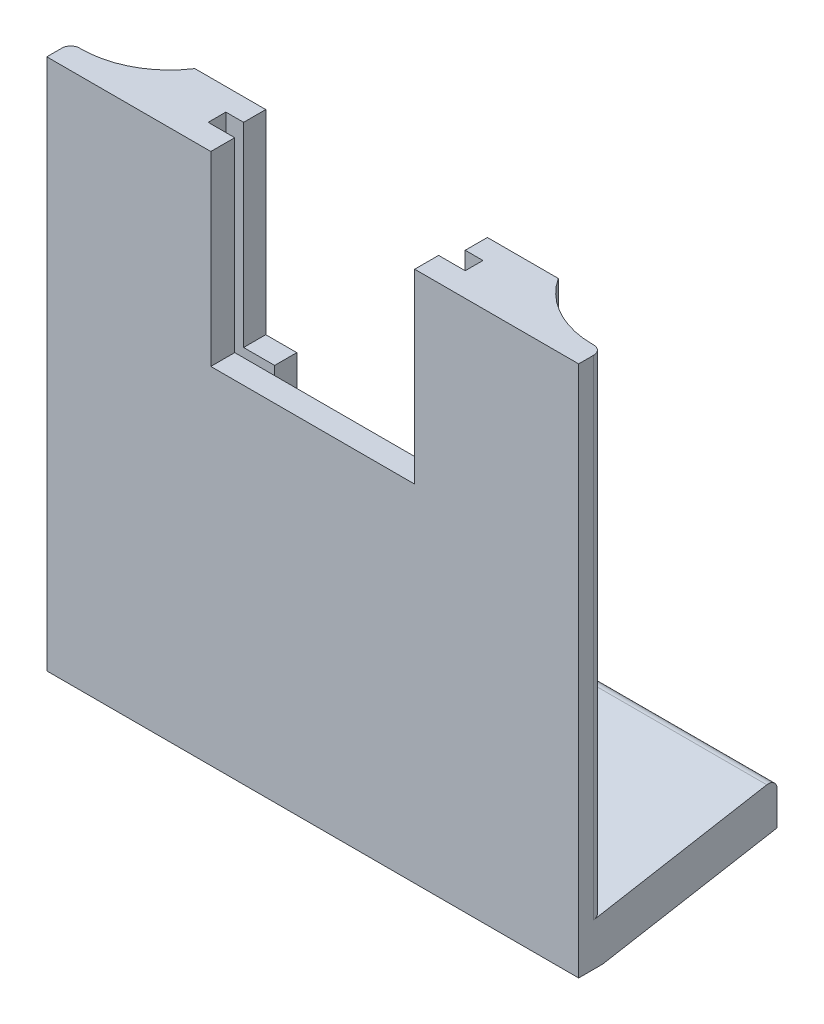
SolidWorks part; units mm, degrees
ref_plane "Front Plane" through (0, 0, 0) normal (0, 0, 1) x (1, 0, 0)
ref_plane "Top Plane" through (0, 0, 0) normal (0, 1, 0) x (1, 0, 0)
ref_plane "Right Plane" through (0, 0, 0) normal (1, 0, 0) x (0, 0, -1)
sketch "Sketch1" plane through (0, 0, 0) normal (0, 0, 1) x (1, 0, 0)
  line L0 (-33.3735, 40.7229) -> (-33.3735, 19.7229) construction
  line L1 (-63.3735, 40.7229) -> (-3.3735, 40.7229)
  line L2 (-63.3735, 40.7229) -> (-63.3735, -19.2771)
  line L3 (-63.3735, -19.2771) -> (-3.3735, -19.2771)
  line L4 (-3.3735, 40.7229) -> (-3.3735, -19.2771)
  line L5 (-44.8735, 19.7229) -> (-21.8735, 19.7229)
  line L6 (-21.8735, 19.7229) -> (-21.8735, 40.7229)
  line L7 (-44.8735, 19.7229) -> (-44.8735, 40.7229)
  dimension "D1" = 60
  dimension "D2" = 60
  dimension "D3" = 11.5
  dimension "D4" = 21
extrude "Boss-Extrude1" add sketch "Sketch1" along normal blind 2.7 contours L5 L7 L1 L2 L3 L4 L6 region at (-33.3735, 7.7012, 0)
sketch "Sketch3" plane through (0, 0, 0) normal (0, 0, -1) x (-1, 0, 0)
  line L0 (44.8735, 19.7229) -> (44.8735, 40.7229) construction
  line L1 (44.8735, 19.7229) -> (21.8735, 19.7229) construction
  line L2 (21.8735, 19.7229) -> (21.8735, 40.7229) construction
  line L3 (44.8735, 19.7229) -> (44.8735, 40.7229) construction
  line L4 (44.8735, 19.7229) -> (21.8735, 19.7229) construction
  line L5 (21.8735, 19.7229) -> (21.8735, 40.7229) construction
  line L6 (18.8735, 16.7229) -> (18.8735, 40.7229)
  line L7 (47.8735, 16.7229) -> (18.8735, 16.7229)
  line L8 (47.8735, 16.7229) -> (47.8735, 40.7229)
  line L9 (53.8735, 10.7229) -> (53.8735, 40.7229)
  line L10 (53.8735, 10.7229) -> (12.8735, 10.7229)
  line L11 (12.8735, 10.7229) -> (12.8735, 40.7229)
  line L12 (12.8735, 40.7229) -> (18.8735, 40.7229)
  line L13 (47.8735, 40.7229) -> (53.8735, 40.7229)
  dimension "D1" = 3
  dimension "D2" = 6
extrude "Boss-Extrude2" add sketch "Sketch3" along normal blind 2
sketch "Sketch4" plane through (0, 0, -2) normal (0, 0, -1) x (-1, 0, 0)
  line L3 (12.8735, 40.7229) -> (12.8735, 10.7229) construction
  line L4 (12.8735, 10.7229) -> (53.8735, 10.7229) construction
  line L5 (53.8735, 10.7229) -> (53.8735, 40.7229) construction
  line L6 (45.8735, 40.7229) -> (45.8735, 18.7229)
  line L7 (45.8735, 18.7229) -> (20.8735, 18.7229)
  line L8 (20.8735, 18.7229) -> (20.8735, 40.7229)
  line L9 (45.8735, 40.7229) -> (45.8735, 18.7229)
  line L10 (45.8735, 18.7229) -> (20.8735, 18.7229)
  line L11 (20.8735, 18.7229) -> (20.8735, 40.7229)
  line L12 (12.8735, 40.7229) -> (12.8735, 10.7229)
  line L13 (12.8735, 10.7229) -> (53.8735, 10.7229)
  line L14 (53.8735, 10.7229) -> (53.8735, 40.7229)
  line L15 (20.8735, 40.7229) -> (12.8735, 40.7229)
  line L16 (45.8735, 40.7229) -> (53.8735, 40.7229)
  dimension "D1" = 2
extrude "Boss-Extrude3" add sketch "Sketch4" along normal blind 2.5
fillet "Fillet1" radius 10 1 edges at (-12.8735, 25.7229, 0)
fillet "Fillet2" radius 10 1 edges at (-53.8735, 25.7229, 0)
fillet "Fillet3" radius 10 1 edges at (-33.3735, 10.7229, 0)
sketch "Sketch5" plane through (0, 0, -4.5) normal (0, 0, -1) x (-1, 0, 0)
  line L0 (33.3735, 18.7229) -> (33.3735, 10.7229) construction
  line L1 (45.8735, 18.7229) -> (20.8735, 18.7229) construction
  line L2 (12.8735, 10.7229) -> (53.8735, 10.7229) construction
  line L3 (33.3735, 10.7229) -> (33.3735, -1.3035) construction
  line L4 (24.3735, -1.3035) -> (42.3735, -1.3035)
  line L5 (42.3735, -1.3035) -> (42.3735, 18.7229)
  line L6 (24.3735, -1.3035) -> (24.3735, 18.7229)
  line L7 (24.3735, 18.7229) -> (42.3735, 18.7229)
  dimension "D1" = 9
extrude "Cut-Extrude1" cut sketch "Sketch5" against normal up to surface (4.5 mm away) up to face at (-33.3735, 29.4729, 0)
sketch "Sketch6" plane through (0, 0, 0) normal (0, 0, -1) x (-1, 0, 0)
  line L0 (63.3735, 40.7229) -> (63.3735, -19.2771) construction
  line L1 (3.3735, -19.2771) -> (63.3735, -19.2771)
  line L2 (3.3735, -19.2771) -> (3.3735, -14.2771)
  line L3 (3.3735, -14.2771) -> (63.3735, -14.2771)
  line L4 (63.3735, -19.2771) -> (63.3735, -14.2771)
  dimension "D1" = 5
extrude "Cut-Extrude5" [suppressed] cut sketch "Sketch6" against normal blind 0.4
sketch "Sketch7" [suppressed] plane through (-3.3735, 0, 0) normal (1, 0, 0) x (0, 0, -1)
  line L0 (-0.4, -19.2771) -> (38.2138, -8.9306) construction
sketch "Sketch9" plane through (0, 0, 0) normal (0, 0, -1) x (-1, 0, 0)
  line L0 (63.3735, 40.7229) -> (63.3735, -19.2771) construction
  line L1 (3.3735, -19.2771) -> (63.3735, -19.2771)
  line L2 (3.3735, -19.2771) -> (3.3735, -14.2771)
  line L3 (3.3735, -14.2771) -> (63.3735, -14.2771)
  line L4 (63.3735, -19.2771) -> (63.3735, -14.2771)
  dimension "D1" = 5
sketch3d "3DSketch1"
  line L0 (-33.3735, -16.7771, 0) -> (-33.3735, -13.3041, -19.6962)
  line L1 (-33.3735, -14.2771, 0) -> (-33.3735, -16.7771, 0) construction
  line L2 (-3.3735, -14.2771, 0) -> (-63.3735, -14.2771, 0) construction
  line L3 (-33.3735, -16.7771, 0) -> (-3.3735, -16.7771, 0) construction
  line L4 (-3.3735, -19.2771, 0) -> (-3.3735, -14.2771, 0) construction
  dimension "D1" = 80
  dimension "D2" = 20
sweep "Sweep1" add profiles "Sketch9" path "3DSketch1"
fillet "Fillet4" radius 1 1 edges at (-63.3735, 13.2229, 0)
fillet "Fillet5" radius 1 1 edges at (-3.3735, 13.2229, 0)
fillet "Fillet6" radius 1 1 edges at (-33.3735, -10.8041, -19.6962)
